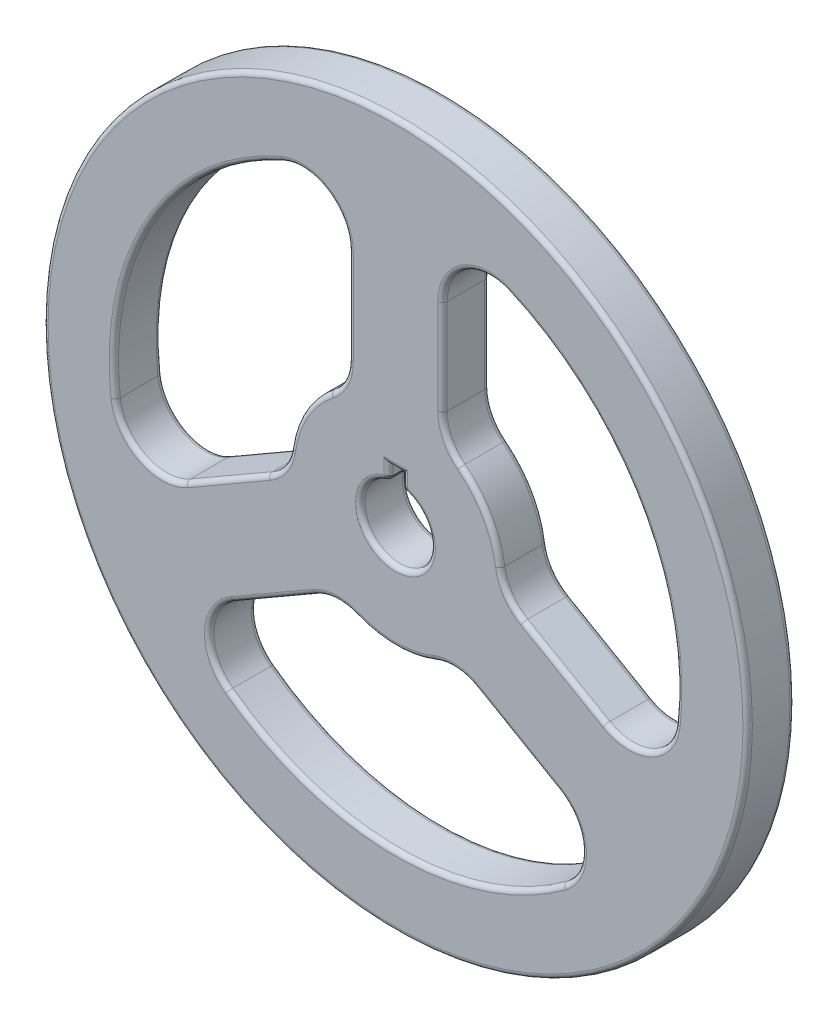
SolidWorks part; units mm, degrees
ref_plane "前视基准面" through (0, 0, 0) normal (0, 0, 1) x (1, 0, 0)
ref_plane "上视基准面" through (0, 0, 0) normal (0, 1, 0) x (1, 0, 0)
ref_plane "右视基准面" through (0, 0, 0) normal (1, 0, 0) x (0, 0, -1)
sketch "草图1" plane through (0, 0, 0) normal (0, 0, 1) x (1, 0, 0)
  circle A0 centre (0, 0) radius 75
  circle A1 centre (0, 0) radius 7.5
  dimension "D1" = 15
  dimension "D2" = 150
extrude "凸台-拉伸1" add sketch "草图1" along normal blind 10
sketch "草图2" plane through (0, 0, 10) normal (0, 0, 1) x (1, 0, 0)
  circle A0 centre (0, 0) radius 60
  circle A1 centre (0, 0) radius 22.5
  circle A2 centre (0, 0) radius 7.5 construction
  circle A3 centre (0, 0) radius 75 construction
  dimension "D1" = 15
  dimension "D2" = 15
extrude "切除-拉伸1" cut sketch "草图2" against normal blind 10
sketch "草图3" plane through (0, 0, 10) normal (0, 0, 1) x (1, 0, 0)
  line L1 (-10, 14.1245) -> (10, 14.1245)
  line L2 (-10, 14.1245) -> (-10, 64.6334)
  line L3 (-10, 64.6334) -> (10, 64.6334)
  line L4 (10, 14.1245) -> (10, 64.6334)
  line L5 (-10, 14.1245) -> (10, 64.6334) construction
  line L6 (-10, 64.6334) -> (10, 14.1245) construction
  point P0 (0, 39.379)
  dimension "D1" = 20
extrude "凸台-拉伸2" add sketch "草图3" against normal blind 10
fillet "圆角1" radius 10 4 edges at (-10, 59.1608, 5) (10, 59.1608, 5) (10, 20.1556, 5) (-10, 20.1556, 5)
pattern_circular "阵列(圆周)1" count 3 over 360 about axis through (0, 0, 0) along (0, 0, 1) of "凸台-拉伸2", "圆角1"
sketch "草图4" plane through (0, 0, 10) normal (0, 0, 1) x (1, 0, 0)
  line L1 (-1.5, 4.5) -> (1.5, 4.5)
  line L2 (-1.5, 4.5) -> (-1.5, 10.5)
  line L3 (-1.5, 10.5) -> (1.5, 10.5)
  line L4 (1.5, 4.5) -> (1.5, 10.5)
  line L5 (-1.5, 4.5) -> (1.5, 10.5) construction
  line L6 (-1.5, 10.5) -> (1.5, 4.5) construction
  circle A0 centre (0, 0) radius 7.5 construction
  point P0 (0, 7.5)
  dimension "D1" = 3
  dimension "D2" = 6
extrude "切除-拉伸2" cut sketch "草图4" against normal blind 10
chamfer "倒角1" distance 0.5 angle 45 2 edges at (1.5, 7.3485, 5) (-1.5, 7.3485, 5)
fillet "圆角2" radius 1 62 edges at (75, 0, 0) (0, -60, 10) (0, -60, 0) (-25.9358, -26.521, 0) (-25.9358, -26.521, 10) (-35.9358, -9.2005, 10) (-35.9358, -9.2005, 0) (0, -22.5, 10) (0, -22.5, 0) (-39.6706, -39.6733, 10) (-39.6706, -39.6733, 0) (-54.1933, -14.5191, 0) (-54.1933, -14.5191, 10) (-23.8939, -1.0787, 0) (-23.8939, -1.0787, 10) (-12.8811, -20.1534, 10) (-12.8811, -20.1534, 0) (51.9615, 30, 0) (51.9615, 30, 10) (35.9358, -9.2005, 0) (35.9358, -9.2005, 10) (25.9358, -26.521, 10) (25.9358, -26.521, 0) (19.4856, 11.25, 0) (19.4856, 11.25, 10) (54.1933, -14.5191, 10) (54.1933, -14.5191, 0) (39.6706, -39.6733, 0) (39.6706, -39.6733, 10) (12.8811, -20.1534, 0) (12.8811, -20.1534, 10) (23.8939, -1.0787, 10) (23.8939, -1.0787, 0) (-1.5, 9.2448, 0) (0, 10.5, 0) (-1.5, 9.2448, 10) (0, 10.5, 10) (1.5, 9.2448, 10) (1.5, 9.2448, 0) (0, -7.5, 10) (-1.7519, 7.6085, 10) (1.7519, 7.6085, 10) (0, -7.5, 0) (-1.7519, 7.6085, 0) (1.7519, 7.6085, 0) (-51.9615, 30, 10) (-51.9615, 30, 0) (-10, 35.7216, 10) (-10, 35.7216, 0) (10, 35.7216, 0) (10, 35.7216, 10) (-19.4856, 11.25, 0) (-19.4856, 11.25, 10) (-14.5228, 54.1924, 10) (-14.5228, 54.1924, 0) (14.5228, 54.1924, 0) (14.5228, 54.1924, 10) (11.0128, 21.2321, 10) (11.0128, 21.2321, 0) (-11.0128, 21.2321, 0) (-11.0128, 21.2321, 10) (75, 0, 10)
